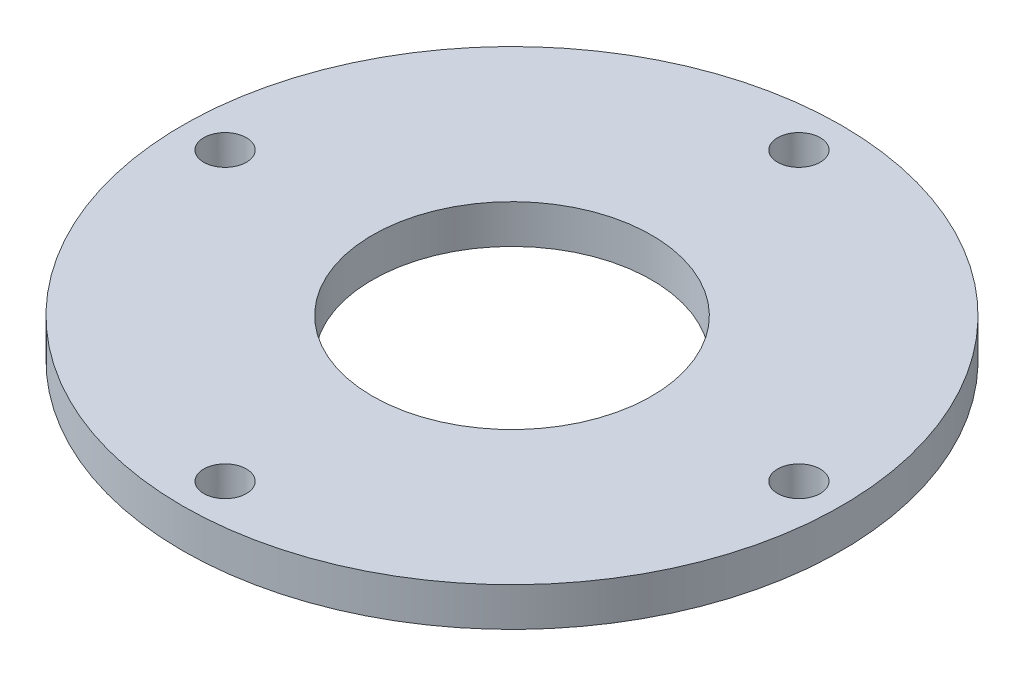
SolidWorks part; units mm, degrees
ref_plane "Front Plane" through (0, 0, 0) normal (0, 0, 1) x (1, 0, 0)
ref_plane "Top Plane" through (0, 0, 0) normal (0, 1, 0) x (1, 0, 0)
ref_plane "Right Plane" through (0, 0, 0) normal (1, 0, 0) x (0, 0, -1)
ref_axis "X" through (-88.99, 0, 0) along (1, 0, 0)
ref_axis "Y" through (0, 0, -88.99) along (0, 0, 1)
ref_axis "Z" through (0, 55, 0) along (0, -1, 0)
sketch "Sketch1" plane through (0, 0, 0) normal (0, 0, 1) x (1, 0, 0)
  line L0 (0, 0) -> (0, -29.6934) construction
  line L9 (-18, 2.5) -> (-42.5, 2.5)
  line L20 (-42.5, 2.5) -> (-42.5, -2.5)
  line L22 (-42.5, -2.5) -> (-31, -2.5)
  line L25 (-26, -2.5) -> (-18, -2.5)
  line L26 (-18, 2.5) -> (-18, -2.5)
  line L29 (-31, -5.5) -> (-26, -5.5)
  line L30 (-26, -2.5) -> (-26, -5.5)
  line L31 (-31, -2.5) -> (-31, -5.5)
  point P7 (-18, 0)
  dimension "D1" = 62
  dimension "D3" = 52
  dimension "D4" = 85
  dimension "D5" = 5
  dimension "D7" = 3
  dimension "D9" = 18
revolve "Revolve1" add sketch "Sketch1" angle 360 about L0
sketch "Sketch9" plane through (0, 2.5, 0) normal (0, 1, 0) x (1, 0, 0)
  line L0 (-88.99, 0) -> (88.99, 0) construction
  point P0 (37, 0)
  point P1 (0, 0)
  point P3 (0, 0)
  point P4 (34.3976, 6.4654)
  point P5 (0, 0)
  dimension "D1" = 37
hole_wizard "M5 Clearance Hole1" positions "3DSketch1" profile "Sketch11" hole size "M5" standard "ANSI Metric" end condition through all
sketch3d "3DSketch1"
  point P0 (37, 2.5, 0)
sketch "Sketch11" plane through (37, 2.5, 0) normal (1, 0, 0) x (0, 0, 1)
  line L0 (0, 0) -> (0, 8)
  line L1 (0, 8) -> (2.75, 8)
  line L2 (2.75, 8) -> (2.75, 0)
  line L5 (2.75, 0) -> (0, 0)
  line L11 (0, -6.35) -> (0, 107.95) construction
  dimension "Thru Hole Dia." = 5.5
  dimension "Thru Hole Depth" = 8
pattern_circular "CirPattern1" count 4 over 360 about axis through (0, 55, 0) along (0, -1, 0) of "M5 Clearance Hole1"
